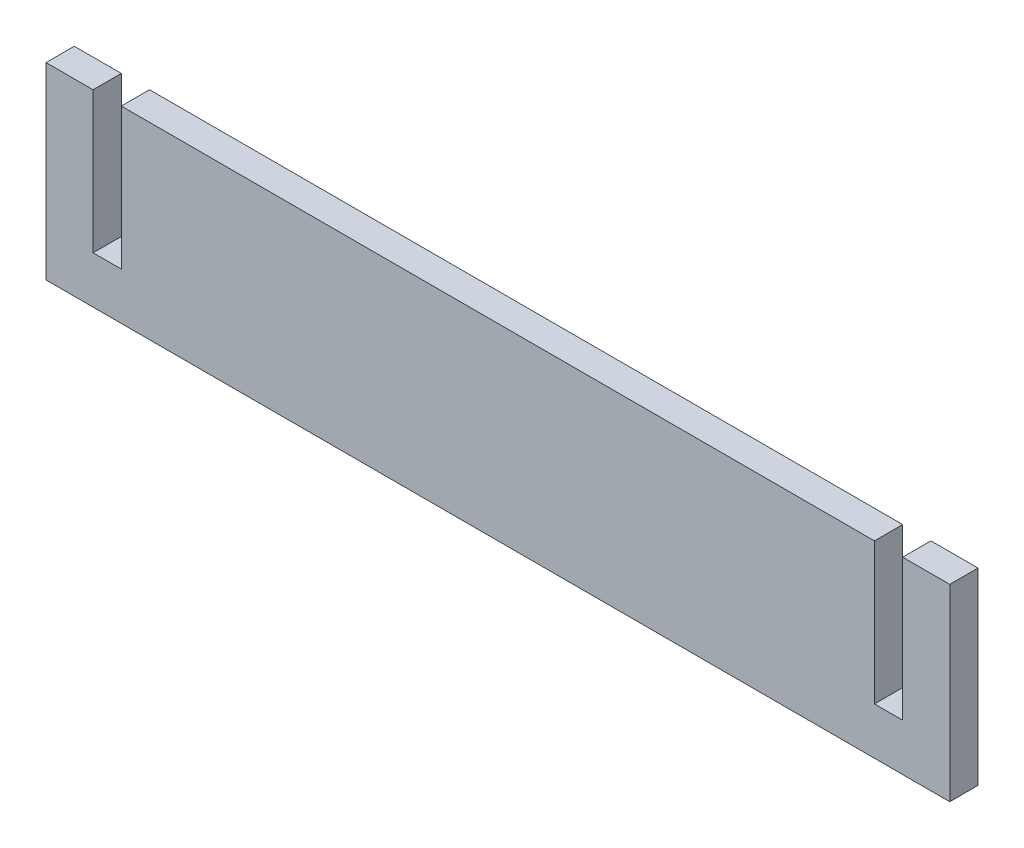
SolidWorks part; units mm, degrees
material "Acrylic (Medium-high impact)"
ref_plane "Front Plane" through (0, 0, 0) normal (0, 0, 1) x (1, 0, 0)
ref_plane "Top Plane" through (0, 0, 0) normal (0, 1, 0) x (1, 0, 0)
ref_plane "Right Plane" through (0, 0, 0) normal (1, 0, 0) x (0, 0, -1)
sketch "Sketch1" plane through (0, 0, 0) normal (0, 0, 1) x (1, 0, 0)
  line L0 (-43, 10) -> (-43, -5)
  line L1 (-48, -10) -> (48, -10)
  line L2 (-48, -10) -> (-48, 10)
  line L3 (-48, 10) -> (-43, 10)
  line L4 (48, -10) -> (48, 10)
  line L5 (-48, -10) -> (48, 10) construction
  line L6 (-48, 10) -> (48, -10) construction
  line L7 (-43, -5) -> (-40, -5)
  line L8 (-40, -5) -> (-40, 10)
  line L9 (40, 10) -> (40, -5)
  line L10 (40, -5) -> (43, -5)
  line L11 (43, -5) -> (43, 10)
  line L12 (43, 10) -> (48, 10)
  line L13 (-40, 10) -> (40, 10)
  point P0 (0, 0)
  dimension "D1" = 3
  dimension "D2" = 80
  dimension "D3" = 5
  dimension "D4" = 20
  dimension "D5" = 5
extrude "Boss-Extrude1" add sketch "Sketch1" along normal blind 3
